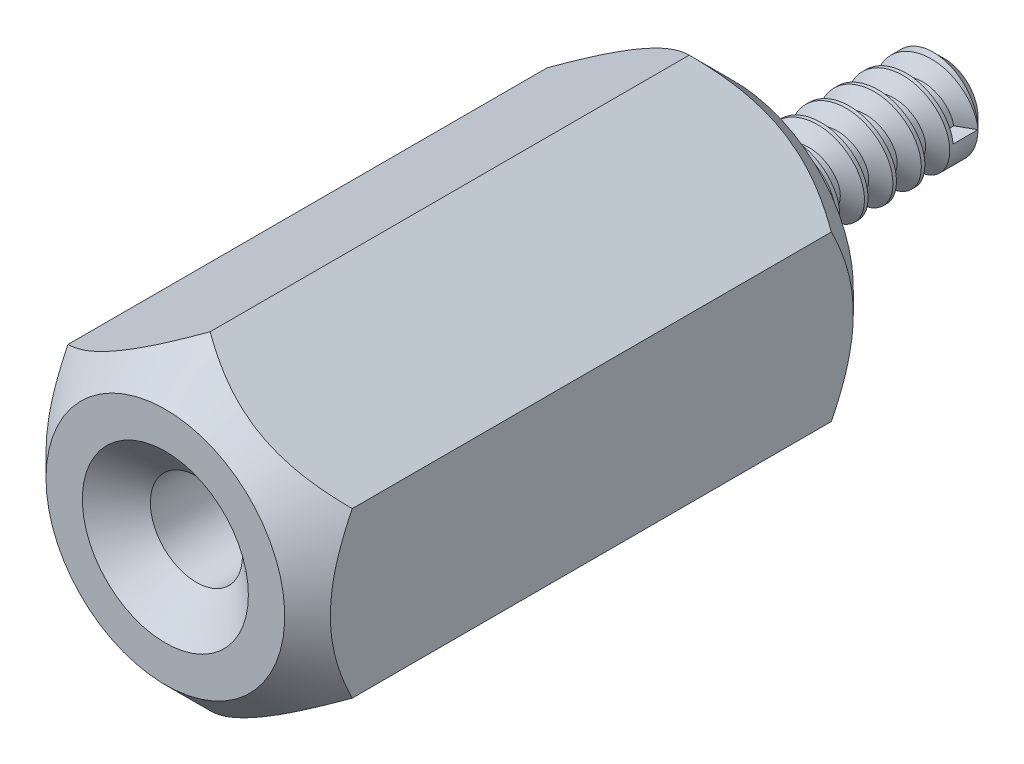
SolidWorks part; units mm, degrees
ref_plane "Front Plane" through (0, 0, 0) normal (0, 0, 1) x (1, 0, 0)
ref_plane "Top Plane" through (0, 0, 0) normal (0, 1, 0) x (1, 0, 0)
ref_plane "Right Plane" through (0, 0, 0) normal (1, 0, 0) x (0, 0, -1)
sketch "Sketch1" plane through (0, 0, 0) normal (0, 0, 1) x (1, 0, 0)
  line L1 (3.175, -1.8331) -> (3.175, 1.8331)
  line L2 (3.175, 1.8331) -> (0, 3.6662)
  line L3 (0, 3.6662) -> (-3.175, 1.8331)
  line L4 (-3.175, 1.8331) -> (-3.175, -1.8331)
  line L5 (-3.175, -1.8331) -> (0, -3.6662)
  line L6 (0, -3.6662) -> (3.175, -1.8331)
  circle A0 centre (0, 0) radius 3.175 construction
  dimension "D1" = 6.35
extrude "Boss-Extrude1" add sketch "Sketch1" along normal blind 6.35 and the other way blind 6.35
ref_axis "Axis1" through (0, 0, -0.635) along (0, 0, 1)
sketch "Sketch3" plane through (0, 0, 0) normal (1, 0, 0) x (0, 0, -1)
  line L0 (-6.35, 3.6662) -> (6.35, 3.6662) construction
  line L1 (-5.35, 3.6662) -> (-6.35, 2.6662)
  line L2 (-6.35, 1.8331) -> (-6.35, 3.6662) construction
  line L3 (-6.35, 2.6662) -> (-6.35, 3.6662)
  line L4 (-6.35, 3.6662) -> (-5.35, 3.6662)
  dimension "D1" = 1
  dimension "D2" = 45
revolve "Cut-Revolve2" cut sketch "Sketch3" angle 360 about axis through (0, 0, -0.635) along (0, 0, 1)
mirror "Mirror1" about plane through (0, 0, 0) normal (0, 0, 1) of "Cut-Revolve2"
hole_wizard "CSK for #1 Flat Head Machine Screw (100)1" positions "Sketch5" profile "Sketch4" countersink size "#1" standard "ANSI Inch"
sketch "Sketch5" plane through (0, 0, 6.35) normal (0, 0, 1) x (1, 0, 0)
  point P0 (0, 0)
sketch "Sketch4" plane through (0, 0, 6.35) normal (1, 0, 0) x (0, -1, 0)
  line L0 (0, 0) -> (0, 10.6181)
  line L1 (0, 10.6181) -> (1.0287, 10)
  line L2 (1.0287, 10) -> (1.0287, 0.6927)
  line L3 (1.0287, 0.6927) -> (1.8542, 0)
  line L5 (1.8542, 0) -> (0, 0)
  line L6 (-1.0287, 0.6927) -> (-1.8542, 0) construction
  line L10 (0, 10.6181) -> (-1.0287, 10) construction
  line L11 (0, -6.35) -> (0, 107.95) construction
  dimension "Hole Dia." = 2.0574
  dimension "Hole Depth" = 10
  dimension "Near C'Sink Dia." = 3.7084
  dimension "Near C'Sink Angle" = 100
  dimension "Drill Angle" = 118
sketch "Sketch6" plane through (0, 0, -6.35) normal (0, 0, -1) x (-1, 0, 0)
  circle A0 centre (0, 0) radius 1
  dimension "D1" = 2
extrude "Boss-Extrude2" add sketch "Sketch6" along normal blind 4.7
chamfer "Chamfer1" distance 0.25 angle 45 1 edges at (-1, 0, -11.05)
thread "Thread1" pitch 0.635 method cut profile "Thread Profile1" start angle 0, offset 0, length 4, pitch 0.635, diameter 2
ref_plane "Plane1" through (1, 0, -10.8) normal (0, -1, 0) x (1, 0, 0)
sketch "Thread Profile1" plane through (1, 0, -10.8) normal (0, -1, 0) x (1, 0, 0)
  line L0 (0, 0) -> (0, 0.635) construction
  line L11 (0, 0) -> (0, 0.5556)
  line L12 (0, 0.5556) -> (-0.3437, 0.3572)
  line L13 (-0.3437, 0.3572) -> (-0.3437, 0.1984)
  line L15 (-0.3437, 0.1984) -> (0, 0)
  line L17 (-0.3437, 0.2778) -> (0, 0.2778) construction
  point P2 (0, 0)
  dimension "Pitch" = 0.635
  dimension "Profile_Angle" = 60
  dimension "Profile_Land" = 0.1588
  dimension "Profile_Height" = 0.3437
